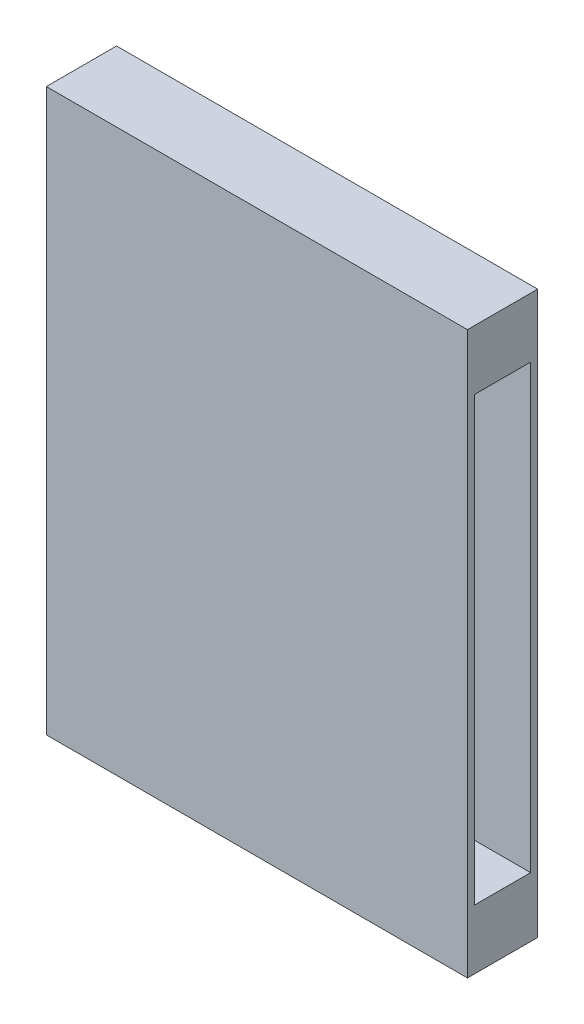
SolidWorks part; units mm, degrees
ref_plane "Top Plane" through (0, 0, 0) normal (0, 0, 1) x (1, 0, 0)
ref_plane "Front Plane" through (0, 0, 0) normal (0, 1, 0) x (1, 0, 0)
ref_plane "Right Plane" through (0, 0, 0) normal (1, 0, 0) x (0, 0, -1)
sketch "Sketch1" plane through (0, 0, 0) normal (0, 0, 1) x (1, 0, 0)
  line L1 (0, 0) -> (30, 0)
  line L2 (0, 0) -> (0, 40)
  line L3 (0, 40) -> (30, 40)
  line L4 (30, 0) -> (30, 40)
  dimension "D1" = 40
  dimension "D2" = 30
extrude "Boss-Extrude1" add sketch "Sketch1" along normal blind 5
sketch "Sketch2" plane through (0, 0, 0) normal (-1, 0, 0) x (0, 0, 1)
  line L14 (0.5, 39.5) -> (0.5, 0.5)
  line L15 (0.5, 0.5) -> (4.5, 0.5)
  line L16 (4.5, 0.5) -> (4.5, 39.5)
  line L17 (4.5, 39.5) -> (0.5, 39.5)
  line L18 (0.5, 39.5) -> (0.5, 0.5)
  line L19 (0.5, 0.5) -> (4.5, 0.5)
  line L20 (4.5, 0.5) -> (4.5, 39.5)
  line L21 (4.5, 39.5) -> (0.5, 39.5)
  dimension "D1" = 0.5
extrude "Cut-Extrude1" cut sketch "Sketch2" against normal blind 21
sketch "Sketch3" plane through (30, 0, 0) normal (1, 0, 0) x (0, 0, -1)
  line L0 (-5, 0) -> (-5, 40) construction
  line L1 (-4.5, 35.75) -> (-0.5, 35.75)
  line L2 (-4.5, 35.75) -> (-4.5, 4.25)
  line L3 (-4.5, 4.25) -> (-0.5, 4.25)
  line L4 (-0.5, 35.75) -> (-0.5, 4.25)
  line L5 (-5, 40) -> (0, 40) construction
  dimension "D1" = 31.5
  dimension "D2" = 4
  dimension "D3" = 0.5
  dimension "D4" = 4.25
extrude "Cut-Extrude2" cut sketch "Sketch3" against normal blind 21
